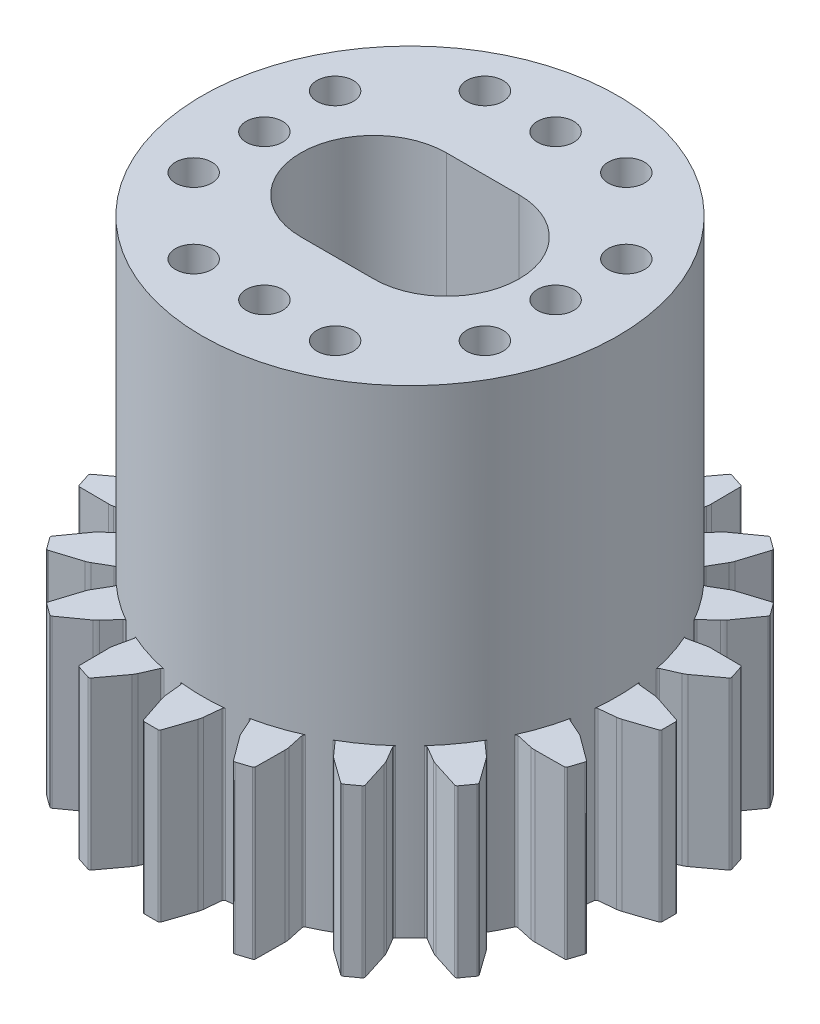
SolidWorks part; units mm, degrees
ref_plane "Front Plane" through (0, 0, 0) normal (0, 0, 1) x (1, 0, 0)
ref_plane "Top Plane" through (0, 0, 0) normal (0, 1, 0) x (1, 0, 0)
ref_plane "Right Plane" through (0, 0, 0) normal (1, 0, 0) x (0, 0, -1)
sketch "Sketch1" plane through (0, 0, 0) normal (0, 1, 0) x (1, 0, 0)
  line L0 (0, 23.8701) -> (0, -17.0658) construction
  line L1 (-0.9919, 10.0309) -> (-0.9111, 10.8389)
  line L2 (-0.8647, 11.0557) -> (-0.4228, 12.3815)
  line L3 (-0.3279, 12.4499) -> (0.3279, 12.4499)
  line L4 (0.4228, 12.3815) -> (0.8647, 11.0557)
  line L5 (0.9111, 10.8389) -> (0.9919, 10.0309)
  line L6 (2.1564, 9.8465) -> (2.4829, 10.59)
  line L7 (2.594, 10.7818) -> (3.424, 11.9062)
  line L8 (3.5353, 11.9419) -> (4.1591, 11.7392)
  line L9 (4.2282, 11.6449) -> (4.2388, 10.2473)
  line L10 (4.2159, 10.0269) -> (4.0431, 9.2334)
  line L11 (5.0936, 8.6982) -> (5.6339, 9.3044)
  line L12 (5.7988, 9.4525) -> (6.9356, 10.2654)
  line L13 (7.0526, 10.2649) -> (7.5831, 9.8794)
  line L14 (7.6197, 9.7683) -> (7.1979, 8.4359)
  line L15 (7.1081, 8.2333) -> (6.6985, 7.5322)
  line L16 (7.5322, 6.6985) -> (8.2333, 7.1081)
  line L17 (8.4359, 7.1979) -> (9.7683, 7.6197)
  line L18 (9.8794, 7.5831) -> (10.2649, 7.0526)
  line L19 (10.2654, 6.9356) -> (9.4525, 5.7988)
  line L20 (9.3044, 5.6339) -> (8.6982, 5.0936)
  line L21 (9.2334, 4.0431) -> (10.0269, 4.2159)
  line L22 (10.2473, 4.2388) -> (11.6449, 4.2282)
  line L23 (11.7392, 4.1591) -> (11.9419, 3.5353)
  line L24 (11.9062, 3.424) -> (10.7818, 2.594)
  line L25 (10.59, 2.4829) -> (9.8465, 2.1564)
  line L26 (10.0309, 0.9919) -> (10.8389, 0.9111)
  line L27 (11.0557, 0.8647) -> (12.3815, 0.4228)
  line L28 (12.4499, 0.3279) -> (12.4499, -0.3279)
  line L29 (12.3815, -0.4228) -> (11.0557, -0.8647)
  line L30 (10.8389, -0.9111) -> (10.0309, -0.9919)
  line L31 (9.8465, -2.1564) -> (10.59, -2.4829)
  line L32 (10.7818, -2.594) -> (11.9062, -3.424)
  line L33 (11.9419, -3.5353) -> (11.7392, -4.1591)
  line L34 (11.6449, -4.2282) -> (10.2473, -4.2388)
  line L35 (10.0269, -4.2159) -> (9.2334, -4.0431)
  line L36 (8.6982, -5.0936) -> (9.3044, -5.6339)
  line L37 (9.4525, -5.7988) -> (10.2654, -6.9356)
  line L38 (10.2649, -7.0526) -> (9.8794, -7.5831)
  line L39 (9.7683, -7.6197) -> (8.4359, -7.1979)
  line L40 (8.2333, -7.1081) -> (7.5322, -6.6985)
  line L41 (6.6985, -7.5322) -> (7.1081, -8.2333)
  line L42 (7.1979, -8.4359) -> (7.6197, -9.7683)
  line L43 (7.5831, -9.8794) -> (7.0526, -10.2649)
  line L44 (6.9356, -10.2654) -> (5.7988, -9.4525)
  line L45 (5.6339, -9.3044) -> (5.0936, -8.6982)
  line L46 (4.0431, -9.2334) -> (4.2159, -10.0269)
  line L47 (4.2388, -10.2473) -> (4.2282, -11.6449)
  line L48 (4.1591, -11.7392) -> (3.5353, -11.9419)
  line L49 (3.424, -11.9062) -> (2.594, -10.7818)
  line L50 (2.4829, -10.59) -> (2.1564, -9.8465)
  line L51 (0.9919, -10.0309) -> (0.9111, -10.8389)
  line L52 (0.8647, -11.0557) -> (0.4228, -12.3815)
  line L53 (0.3279, -12.4499) -> (-0.3279, -12.4499)
  line L54 (-0.4228, -12.3815) -> (-0.8647, -11.0557)
  line L55 (-0.9111, -10.8389) -> (-0.9919, -10.0309)
  line L56 (-2.1564, -9.8465) -> (-2.4829, -10.59)
  line L57 (-2.594, -10.7818) -> (-3.424, -11.9062)
  line L58 (-3.5353, -11.9419) -> (-4.1591, -11.7392)
  line L59 (-4.2282, -11.6449) -> (-4.2388, -10.2473)
  line L60 (-4.2159, -10.0269) -> (-4.0431, -9.2334)
  line L61 (-5.0936, -8.6982) -> (-5.6339, -9.3044)
  line L62 (-5.7988, -9.4525) -> (-6.9356, -10.2654)
  line L63 (-7.0526, -10.2649) -> (-7.5831, -9.8794)
  line L64 (-7.6197, -9.7683) -> (-7.1979, -8.4359)
  line L65 (-7.1081, -8.2333) -> (-6.6985, -7.5322)
  line L66 (-7.5322, -6.6985) -> (-8.2333, -7.1081)
  line L67 (-8.4359, -7.1979) -> (-9.7683, -7.6197)
  line L68 (-9.8794, -7.5831) -> (-10.2649, -7.0526)
  line L69 (-10.2654, -6.9356) -> (-9.4525, -5.7988)
  line L70 (-9.3044, -5.6339) -> (-8.6982, -5.0936)
  line L71 (-9.2334, -4.0431) -> (-10.0269, -4.2159)
  line L72 (-10.2473, -4.2388) -> (-11.6449, -4.2282)
  line L73 (-11.7392, -4.1591) -> (-11.9419, -3.5353)
  line L74 (-11.9062, -3.424) -> (-10.7818, -2.594)
  line L75 (-10.59, -2.4829) -> (-9.8465, -2.1564)
  line L76 (-10.0309, -0.9919) -> (-10.8389, -0.9111)
  line L77 (-11.0557, -0.8647) -> (-12.3815, -0.4228)
  line L78 (-12.4499, -0.3279) -> (-12.4499, 0.3279)
  line L79 (-12.3815, 0.4228) -> (-11.0557, 0.8647)
  line L80 (-10.8389, 0.9111) -> (-10.0309, 0.9919)
  line L81 (-9.8465, 2.1564) -> (-10.59, 2.4829)
  line L82 (-10.7818, 2.594) -> (-11.9062, 3.424)
  line L83 (-11.9419, 3.5353) -> (-11.7392, 4.1591)
  line L84 (-11.6449, 4.2282) -> (-10.2473, 4.2388)
  line L85 (-10.0269, 4.2159) -> (-9.2334, 4.0431)
  line L86 (-8.6982, 5.0936) -> (-9.3044, 5.6339)
  line L87 (-9.4525, 5.7988) -> (-10.2654, 6.9356)
  line L88 (-10.2649, 7.0526) -> (-9.8794, 7.5831)
  line L89 (-9.7683, 7.6197) -> (-8.4359, 7.1979)
  line L90 (-8.2333, 7.1081) -> (-7.5322, 6.6985)
  line L91 (-6.6985, 7.5322) -> (-7.1081, 8.2333)
  line L92 (-7.1979, 8.4359) -> (-7.6197, 9.7683)
  line L93 (-7.5831, 9.8794) -> (-7.0526, 10.2649)
  line L94 (-6.9356, 10.2654) -> (-5.7988, 9.4525)
  line L95 (-5.6339, 9.3044) -> (-5.0936, 8.6982)
  line L96 (-4.0431, 9.2334) -> (-4.2159, 10.0269)
  line L97 (-4.2388, 10.2473) -> (-4.2282, 11.6449)
  line L98 (-4.1591, 11.7392) -> (-3.5353, 11.9419)
  line L99 (-3.424, 11.9062) -> (-2.594, 10.7818)
  line L100 (-2.4829, 10.59) -> (-2.1564, 9.8465)
  arc A0 (-1.0806, 9.9414) -> (-2.0444, 9.7888) centre (0, 0) ccw
  arc A1 (0.8647, 11.0557) -> (0.9111, 10.8389) centre (-0.0839, 10.7394) cw
  arc A2 (-0.9111, 10.8389) -> (-0.8647, 11.0557) centre (0.0839, 10.7394) cw
  arc A3 (0.3279, 12.4499) -> (0.4228, 12.3815) centre (0.3279, 12.3499) cw
  arc A4 (-0.4228, 12.3815) -> (-0.3279, 12.4499) centre (-0.3279, 12.3499) cw
  arc A5 (0.9919, 10.0309) -> (1.0806, 9.9414) centre (1.0914, 10.0409) ccw
  arc A6 (-0.9919, 10.0309) -> (-1.0806, 9.9414) centre (-1.0914, 10.0409) cw
  arc A7 (2.1564, 9.8465) -> (2.0444, 9.7888) centre (2.0648, 9.8867) cw
  arc A8 (2.4829, 10.59) -> (2.594, 10.7818) centre (3.3985, 10.1879) cw
  arc A9 (3.424, 11.9062) -> (3.5353, 11.9419) centre (3.5044, 11.8468) cw
  arc A10 (4.1591, 11.7392) -> (4.2282, 11.6449) centre (4.1282, 11.6441) cw
  arc A11 (4.2388, 10.2473) -> (4.2159, 10.0269) centre (3.2388, 10.2397) cw
  arc A12 (4.0431, 9.2334) -> (4.0998, 9.121) centre (4.1408, 9.2122) ccw
  arc A13 (5.0936, 8.6982) -> (4.9692, 8.678) centre (5.0189, 8.7647) cw
  arc A14 (5.6339, 9.3044) -> (5.7988, 9.4525) centre (6.3804, 8.639) cw
  arc A15 (6.9356, 10.2654) -> (7.0526, 10.2649) centre (6.9938, 10.184) cw
  arc A16 (7.5831, 9.8794) -> (7.6197, 9.7683) centre (7.5244, 9.7985) cw
  arc A17 (7.1979, 8.4359) -> (7.1081, 8.2333) centre (6.2446, 8.7377) cw
  arc A18 (6.6985, 7.5322) -> (6.7177, 7.4076) centre (6.7848, 7.4817) ccw
  arc A19 (7.5322, 6.6985) -> (7.4076, 6.7177) centre (7.4817, 6.7848) cw
  arc A20 (8.2333, 7.1081) -> (8.4359, 7.1979) centre (8.7377, 6.2446) cw
  arc A21 (9.7683, 7.6197) -> (9.8794, 7.5831) centre (9.7985, 7.5244) cw
  arc A22 (10.2649, 7.0526) -> (10.2654, 6.9356) centre (10.184, 6.9938) cw
  arc A23 (9.4525, 5.7988) -> (9.3044, 5.6339) centre (8.639, 6.3804) cw
  arc A24 (8.6982, 5.0936) -> (8.678, 4.9692) centre (8.7647, 5.0189) ccw
  arc A25 (9.2334, 4.0431) -> (9.121, 4.0998) centre (9.2122, 4.1408) cw
  arc A26 (10.0269, 4.2159) -> (10.2473, 4.2388) centre (10.2397, 3.2388) cw
  arc A27 (11.6449, 4.2282) -> (11.7392, 4.1591) centre (11.6441, 4.1282) cw
  arc A28 (11.9419, 3.5353) -> (11.9062, 3.424) centre (11.8468, 3.5044) cw
  arc A29 (10.7818, 2.594) -> (10.59, 2.4829) centre (10.1879, 3.3985) cw
  arc A30 (9.8465, 2.1564) -> (9.7888, 2.0444) centre (9.8867, 2.0648) ccw
  arc A31 (10.0309, 0.9919) -> (9.9414, 1.0806) centre (10.0409, 1.0914) cw
  arc A32 (10.8389, 0.9111) -> (11.0557, 0.8647) centre (10.7394, -0.0839) cw
  arc A33 (12.3815, 0.4228) -> (12.4499, 0.3279) centre (12.3499, 0.3279) cw
  arc A34 (12.4499, -0.3279) -> (12.3815, -0.4228) centre (12.3499, -0.3279) cw
  arc A35 (11.0557, -0.8647) -> (10.8389, -0.9111) centre (10.7394, 0.0839) cw
  arc A36 (10.0309, -0.9919) -> (9.9414, -1.0806) centre (10.0409, -1.0914) ccw
  arc A37 (9.8465, -2.1564) -> (9.7888, -2.0444) centre (9.8867, -2.0648) cw
  arc A38 (10.59, -2.4829) -> (10.7818, -2.594) centre (10.1879, -3.3985) cw
  arc A39 (11.9062, -3.424) -> (11.9419, -3.5353) centre (11.8468, -3.5044) cw
  arc A40 (11.7392, -4.1591) -> (11.6449, -4.2282) centre (11.6441, -4.1282) cw
  arc A41 (10.2473, -4.2388) -> (10.0269, -4.2159) centre (10.2397, -3.2388) cw
  arc A42 (9.2334, -4.0431) -> (9.121, -4.0998) centre (9.2122, -4.1408) ccw
  arc A43 (8.6982, -5.0936) -> (8.678, -4.9692) centre (8.7647, -5.0189) cw
  arc A44 (9.3044, -5.6339) -> (9.4525, -5.7988) centre (8.639, -6.3804) cw
  arc A45 (10.2654, -6.9356) -> (10.2649, -7.0526) centre (10.184, -6.9938) cw
  arc A46 (9.8794, -7.5831) -> (9.7683, -7.6197) centre (9.7985, -7.5244) cw
  arc A47 (8.4359, -7.1979) -> (8.2333, -7.1081) centre (8.7377, -6.2446) cw
  arc A48 (7.5322, -6.6985) -> (7.4076, -6.7177) centre (7.4817, -6.7848) ccw
  arc A49 (6.6985, -7.5322) -> (6.7177, -7.4076) centre (6.7848, -7.4817) cw
  arc A50 (7.1081, -8.2333) -> (7.1979, -8.4359) centre (6.2446, -8.7377) cw
  arc A51 (7.6197, -9.7683) -> (7.5831, -9.8794) centre (7.5244, -9.7985) cw
  arc A52 (7.0526, -10.2649) -> (6.9356, -10.2654) centre (6.9938, -10.184) cw
  arc A53 (5.7988, -9.4525) -> (5.6339, -9.3044) centre (6.3804, -8.639) cw
  arc A54 (5.0936, -8.6982) -> (4.9692, -8.678) centre (5.0189, -8.7647) ccw
  arc A55 (4.0431, -9.2334) -> (4.0998, -9.121) centre (4.1408, -9.2122) cw
  arc A56 (4.2159, -10.0269) -> (4.2388, -10.2473) centre (3.2388, -10.2397) cw
  arc A57 (4.2282, -11.6449) -> (4.1591, -11.7392) centre (4.1282, -11.6441) cw
  arc A58 (3.5353, -11.9419) -> (3.424, -11.9062) centre (3.5044, -11.8468) cw
  arc A59 (2.594, -10.7818) -> (2.4829, -10.59) centre (3.3985, -10.1879) cw
  arc A60 (2.1564, -9.8465) -> (2.0444, -9.7888) centre (2.0648, -9.8867) ccw
  arc A61 (0.9919, -10.0309) -> (1.0806, -9.9414) centre (1.0914, -10.0409) cw
  arc A62 (0.9111, -10.8389) -> (0.8647, -11.0557) centre (-0.0839, -10.7394) cw
  arc A63 (0.4228, -12.3815) -> (0.3279, -12.4499) centre (0.3279, -12.3499) cw
  arc A64 (-0.3279, -12.4499) -> (-0.4228, -12.3815) centre (-0.3279, -12.3499) cw
  arc A65 (-0.8647, -11.0557) -> (-0.9111, -10.8389) centre (0.0839, -10.7394) cw
  arc A66 (-0.9919, -10.0309) -> (-1.0806, -9.9414) centre (-1.0914, -10.0409) ccw
  arc A67 (-2.1564, -9.8465) -> (-2.0444, -9.7888) centre (-2.0648, -9.8867) cw
  arc A68 (-2.4829, -10.59) -> (-2.594, -10.7818) centre (-3.3985, -10.1879) cw
  arc A69 (-3.424, -11.9062) -> (-3.5353, -11.9419) centre (-3.5044, -11.8468) cw
  arc A70 (-4.1591, -11.7392) -> (-4.2282, -11.6449) centre (-4.1282, -11.6441) cw
  arc A71 (-4.2388, -10.2473) -> (-4.2159, -10.0269) centre (-3.2388, -10.2397) cw
  arc A72 (-4.0431, -9.2334) -> (-4.0998, -9.121) centre (-4.1408, -9.2122) ccw
  arc A73 (-5.0936, -8.6982) -> (-4.9692, -8.678) centre (-5.0189, -8.7647) cw
  arc A74 (-5.6339, -9.3044) -> (-5.7988, -9.4525) centre (-6.3804, -8.639) cw
  arc A75 (-6.9356, -10.2654) -> (-7.0526, -10.2649) centre (-6.9938, -10.184) cw
  arc A76 (-7.5831, -9.8794) -> (-7.6197, -9.7683) centre (-7.5244, -9.7985) cw
  arc A77 (-7.1979, -8.4359) -> (-7.1081, -8.2333) centre (-6.2446, -8.7377) cw
  arc A78 (-6.6985, -7.5322) -> (-6.7177, -7.4076) centre (-6.7848, -7.4817) ccw
  arc A79 (-7.5322, -6.6985) -> (-7.4076, -6.7177) centre (-7.4817, -6.7848) cw
  arc A80 (-8.2333, -7.1081) -> (-8.4359, -7.1979) centre (-8.7377, -6.2446) cw
  arc A81 (-9.7683, -7.6197) -> (-9.8794, -7.5831) centre (-9.7985, -7.5244) cw
  arc A82 (-10.2649, -7.0526) -> (-10.2654, -6.9356) centre (-10.184, -6.9938) cw
  arc A83 (-9.4525, -5.7988) -> (-9.3044, -5.6339) centre (-8.639, -6.3804) cw
  arc A84 (-8.6982, -5.0936) -> (-8.678, -4.9692) centre (-8.7647, -5.0189) ccw
  arc A85 (-9.2334, -4.0431) -> (-9.121, -4.0998) centre (-9.2122, -4.1408) cw
  arc A86 (-10.0269, -4.2159) -> (-10.2473, -4.2388) centre (-10.2397, -3.2388) cw
  arc A87 (-11.6449, -4.2282) -> (-11.7392, -4.1591) centre (-11.6441, -4.1282) cw
  arc A88 (-11.9419, -3.5353) -> (-11.9062, -3.424) centre (-11.8468, -3.5044) cw
  arc A89 (-10.7818, -2.594) -> (-10.59, -2.4829) centre (-10.1879, -3.3985) cw
  arc A90 (-9.8465, -2.1564) -> (-9.7888, -2.0444) centre (-9.8867, -2.0648) ccw
  arc A91 (-10.0309, -0.9919) -> (-9.9414, -1.0806) centre (-10.0409, -1.0914) cw
  arc A92 (-10.8389, -0.9111) -> (-11.0557, -0.8647) centre (-10.7394, 0.0839) cw
  arc A93 (-12.3815, -0.4228) -> (-12.4499, -0.3279) centre (-12.3499, -0.3279) cw
  arc A94 (-12.4499, 0.3279) -> (-12.3815, 0.4228) centre (-12.3499, 0.3279) cw
  arc A95 (-11.0557, 0.8647) -> (-10.8389, 0.9111) centre (-10.7394, -0.0839) cw
  arc A96 (-10.0309, 0.9919) -> (-9.9414, 1.0806) centre (-10.0409, 1.0914) ccw
  arc A97 (-9.8465, 2.1564) -> (-9.7888, 2.0444) centre (-9.8867, 2.0648) cw
  arc A98 (-10.59, 2.4829) -> (-10.7818, 2.594) centre (-10.1879, 3.3985) cw
  arc A99 (-11.9062, 3.424) -> (-11.9419, 3.5353) centre (-11.8468, 3.5044) cw
  arc A100 (-11.7392, 4.1591) -> (-11.6449, 4.2282) centre (-11.6441, 4.1282) cw
  arc A101 (-10.2473, 4.2388) -> (-10.0269, 4.2159) centre (-10.2397, 3.2388) cw
  arc A102 (-9.2334, 4.0431) -> (-9.121, 4.0998) centre (-9.2122, 4.1408) ccw
  arc A103 (-8.6982, 5.0936) -> (-8.678, 4.9692) centre (-8.7647, 5.0189) cw
  arc A104 (-9.3044, 5.6339) -> (-9.4525, 5.7988) centre (-8.639, 6.3804) cw
  arc A105 (-10.2654, 6.9356) -> (-10.2649, 7.0526) centre (-10.184, 6.9938) cw
  arc A106 (-9.8794, 7.5831) -> (-9.7683, 7.6197) centre (-9.7985, 7.5244) cw
  arc A107 (-8.4359, 7.1979) -> (-8.2333, 7.1081) centre (-8.7377, 6.2446) cw
  arc A108 (-7.5322, 6.6985) -> (-7.4076, 6.7177) centre (-7.4817, 6.7848) ccw
  arc A109 (-6.6985, 7.5322) -> (-6.7177, 7.4076) centre (-6.7848, 7.4817) cw
  arc A110 (-7.1081, 8.2333) -> (-7.1979, 8.4359) centre (-6.2446, 8.7377) cw
  arc A111 (-7.6197, 9.7683) -> (-7.5831, 9.8794) centre (-7.5244, 9.7985) cw
  arc A112 (-7.0526, 10.2649) -> (-6.9356, 10.2654) centre (-6.9938, 10.184) cw
  arc A113 (-5.7988, 9.4525) -> (-5.6339, 9.3044) centre (-6.3804, 8.639) cw
  arc A114 (-5.0936, 8.6982) -> (-4.9692, 8.678) centre (-5.0189, 8.7647) ccw
  arc A115 (-4.0431, 9.2334) -> (-4.0998, 9.121) centre (-4.1408, 9.2122) cw
  arc A116 (-4.2159, 10.0269) -> (-4.2388, 10.2473) centre (-3.2388, 10.2397) cw
  arc A117 (-4.2282, 11.6449) -> (-4.1591, 11.7392) centre (-4.1282, 11.6441) cw
  arc A118 (-3.5353, 11.9419) -> (-3.424, 11.9062) centre (-3.5044, 11.8468) cw
  arc A119 (-2.594, 10.7818) -> (-2.4829, 10.59) centre (-3.3985, 10.1879) cw
  arc A120 (-2.1564, 9.8465) -> (-2.0444, 9.7888) centre (-2.0648, 9.8867) ccw
  arc A121 (-4.0998, 9.121) -> (-4.9692, 8.678) centre (0, 0) ccw
  arc A122 (-6.7177, 7.4076) -> (-7.4076, 6.7177) centre (0, 0) ccw
  arc A123 (-8.678, 4.9692) -> (-9.121, 4.0998) centre (0, 0) ccw
  arc A124 (-9.7888, 2.0444) -> (-9.9414, 1.0806) centre (0, 0) ccw
  arc A125 (-9.121, -4.0998) -> (-8.678, -4.9692) centre (0, 0) ccw
  arc A126 (-7.4076, -6.7177) -> (-6.7177, -7.4076) centre (0, 0) ccw
  arc A127 (-4.9692, -8.678) -> (-4.0998, -9.121) centre (0, 0) ccw
  arc A128 (-2.0444, -9.7888) -> (-1.0806, -9.9414) centre (0, 0) ccw
  arc A129 (1.0806, -9.9414) -> (2.0444, -9.7888) centre (0, 0) ccw
  arc A130 (4.0998, -9.121) -> (4.9692, -8.678) centre (0, 0) ccw
  arc A131 (6.7177, -7.4076) -> (7.4076, -6.7177) centre (0, 0) ccw
  arc A132 (8.678, -4.9692) -> (9.121, -4.0998) centre (0, 0) ccw
  arc A133 (9.7888, -2.0444) -> (9.9414, -1.0806) centre (0, 0) ccw
  arc A134 (9.9414, 1.0806) -> (9.7888, 2.0444) centre (0, 0) ccw
  arc A135 (9.121, 4.0998) -> (8.678, 4.9692) centre (0, 0) ccw
  arc A136 (7.4076, 6.7177) -> (6.7177, 7.4076) centre (0, 0) ccw
  arc A137 (4.9692, 8.678) -> (4.0998, 9.121) centre (0, 0) ccw
  arc A138 (2.0444, 9.7888) -> (1.0806, 9.9414) centre (0, 0) ccw
  arc A139 (-9.9414, -1.0806) -> (-9.7888, -2.0444) centre (0, 0) ccw
  point P7 (0, 12.4499)
  point P12 (0, 10)
  point P21 (0.9, 10.9499)
  point P24 (-0.9, 10.9499)
  point P27 (0.4, 12.4499)
  point P30 (-0.4, 12.4499)
  point P32 (1, 9.9499)
  point P35 (-1, 9.9499)
  point P374 (0, 0)
  dimension "D1" = 20
  dimension "D9" = 1
  dimension "D10" = 0.1
  dimension "D11" = 0.1
  dimension "D2" = 0.8
  dimension "D3" = 1
  dimension "D4" = 2.5
  dimension "D5" = 1
  dimension "D6" = 2
  dimension "D7" = 0.1
  dimension "D8" = 0.1
  dimension "D12" = 20
extrude "Boss-Extrude1" add sketch "Sketch1" along normal blind 8
sketch "Sketch2" plane through (0, 0, 0) normal (0, -1, 0) x (1, 0, 0)
  circle A0 centre (0, 0) radius 8
  circle A1 centre (0, 0) radius 5.5
  dimension "D1" = 16
  dimension "D2" = 11
extrude "Cut-Extrude1" cut sketch "Sketch2" against normal blind 2.9
sketch "Sketch3" plane through (0, 8, 0) normal (0, 1, 0) x (1, 0, 0)
  circle A0 centre (0, 0) radius 10
  dimension "D1" = 20
extrude "Boss-Extrude2" add sketch "Sketch3" along normal blind 15
sketch "Sketch4" plane through (0, 23, 0) normal (0, 1, 0) x (1, 0, 0)
  circle A0 centre (0, 7) radius 0.875
  circle A1 centre (3.4, 7) radius 0.875
  circle A2 centre (-3.4, 7) radius 0.875
  circle A3 centre (7, 3.4) radius 0.875
  circle A4 centre (7, 0) radius 0.875
  circle A5 centre (7, -3.4) radius 0.875
  circle A6 centre (3.4, -7) radius 0.875
  circle A7 centre (0, -7) radius 0.875
  circle A8 centre (-3.4, -7) radius 0.875
  circle A9 centre (-7, -3.4) radius 0.875
  circle A10 centre (-7, 0) radius 0.875
  circle A11 centre (-7, 3.4) radius 0.875
  point P27 (0, 0)
  dimension "D5" = 1.75
  dimension "D1" = 7
  dimension "D2" = 7
  dimension "D3" = 4
  dimension "D6" = 3.4
  dimension "D7" = 3.4
extrude "Cut-Extrude2" cut sketch "Sketch4" against normal blind 15
sketch "Sketch5" plane through (0, 0, 0) normal (0, -1, 0) x (1, 0, 0)
  line L0 (-1.75, 3.5) -> (1.75, 3.5)
  line L1 (-1.75, -3.5) -> (1.75, -3.5)
  line L2 (-1.75, 0) -> (1.75, 0) construction
  arc A0 (-1.75, 3.5) -> (-1.75, -3.5) centre (-1.75, 0) ccw
  arc A1 (1.75, -3.5) -> (1.75, 3.5) centre (1.75, 0) ccw
  point P6 (0, 0)
  dimension "D2" = 3.5
  dimension "D1" = 3.5
extrude "Cut-Extrude5" cut sketch "Sketch5" along direction (0, 1, 0) on the side against the normal blind 30 and the other way through all
sketch "Sketch6" plane through (0, 23, 0) normal (0, 1, 0) x (1, 0, 0)
  line L0 (-18.0612, 0) -> (18.3147, 0) construction
  line L1 (0, 13.2248) -> (0, -13.8666) construction
  circle A0 centre (0.1267, 0) radius 2.1107
  point P5 (0, 0)
ref_point "Point1"
